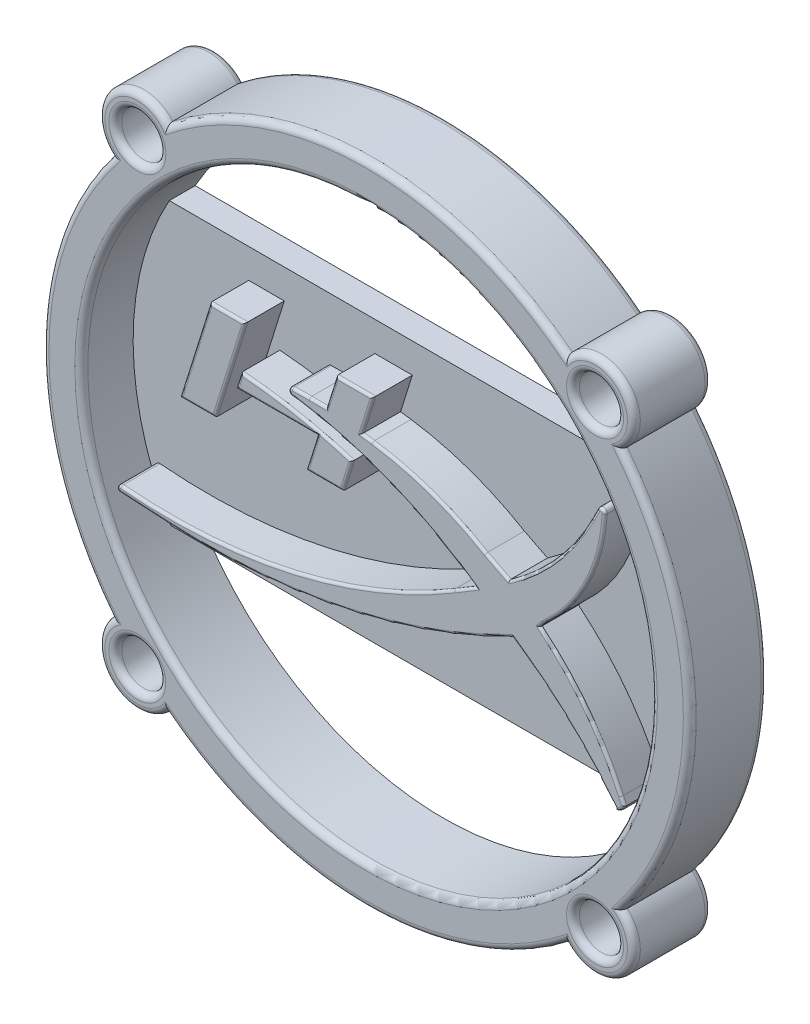
SolidWorks part; units mm, degrees
ref_plane "前视基准面" through (0, 0, 0) normal (0, 0, 1) x (1, 0, 0)
ref_plane "上视基准面" through (0, 0, 0) normal (0, 1, 0) x (1, 0, 0)
ref_plane "右视基准面" through (0, 0, 0) normal (1, 0, 0) x (0, 0, -1)
other "Configuration Table"
sketch "草图1" plane through (0, 0, 0) normal (0, 0, 1) x (1, 0, 0)
  line L0 (0, 0) -> (47.3992, 0) construction
  line L1 (0, 0) -> (0, 44.4048) construction
  line L2 (0, 0) -> (38.3112, 38.3112) construction
  line L3 (0, 0) -> (17.6777, -17.6777) construction
  circle A0 centre (0, 0) radius 25
  circle A1 centre (-17.6777, 17.6777) radius 3
  circle A2 centre (17.6777, 17.6777) radius 3
  circle A3 centre (17.6777, -17.6777) radius 3
  circle A4 centre (-17.6777, -17.6777) radius 3
  point P22 (0, 0)
  dimension "D1" = 50
  dimension "D4" = 6
  dimension "D2" = 45
  dimension "D3" = 45
  dimension "D6" = 17.6777
  dimension "D5" = 4
extrude "凸台-拉伸1" add sketch "草图1" along normal blind 6 contours A0 A1 | A4 A0 A3 A2 A1 | A0 A2 | A0 A2 | A0 A1 | A0 A4 | A0 A4 | A0 A3 | A0 A3 region at (0, 0, 0) region at (16.7548, 16.7548, 0) region at (18.5547, 18.5547, 0) region at (18.5547, -18.5547, 0) region at (16.7548, -16.7548, 0) region at (-16.7548, 16.7548, 0) region at (-18.5547, 18.5547, 0) region at (-18.5547, -18.5547, 0) region at (-16.7548, -16.7548, 0)
sketch "草图2" plane through (0, 0, 6) normal (0, 0, 1) x (1, 0, 0)
  arc A0 (-15.4329, 19.6679) -> (-19.6679, 15.4329) centre (-17.6777, 17.6777) ccw construction
  arc A1 (-15.4329, 19.6679) -> (-19.6679, 15.4329) centre (-17.6777, 17.6777) ccw
  circle A2 centre (17.6777, 17.6777) radius 1.7
  circle A3 centre (17.6777, -17.6777) radius 1.7
  circle A4 centre (-17.6777, -17.6777) radius 1.7
  circle A5 centre (-17.6777, 17.6777) radius 1.7
  arc A10 (-15.4329, 19.6679) -> (-19.6679, 15.4329) centre (-17.6777, 17.6777) ccw
  arc A11 (-19.6679, 15.4329) -> (-19.6679, -15.4329) centre (0, 0) ccw
  arc A12 (-19.6679, -15.4329) -> (-15.4329, -19.6679) centre (-17.6777, -17.6777) ccw
  arc A13 (-15.4329, -19.6679) -> (15.4329, -19.6679) centre (0, 0) ccw
  arc A14 (15.4329, -19.6679) -> (19.6679, -15.4329) centre (17.6777, -17.6777) ccw
  arc A15 (19.6679, -15.4329) -> (19.6679, 15.4329) centre (0, 0) ccw
  arc A16 (19.6679, 15.4329) -> (15.4329, 19.6679) centre (17.6777, 17.6777) ccw
  arc A17 (15.4329, 19.6679) -> (-15.4329, 19.6679) centre (0, 0) ccw
  arc A18 (-15.4329, 19.6679) -> (-19.6679, 15.4329) centre (-17.6777, 17.6777) ccw
  arc A19 (-19.6679, 15.4329) -> (-19.6679, -15.4329) centre (0, 0) ccw
  arc A20 (-19.6679, -15.4329) -> (-15.4329, -19.6679) centre (-17.6777, -17.6777) ccw
  arc A21 (-15.4329, -19.6679) -> (15.4329, -19.6679) centre (0, 0) ccw
  arc A22 (15.4329, -19.6679) -> (19.6679, -15.4329) centre (17.6777, -17.6777) ccw
  arc A23 (19.6679, -15.4329) -> (19.6679, 15.4329) centre (0, 0) ccw
  arc A24 (19.6679, 15.4329) -> (15.4329, 19.6679) centre (17.6777, 17.6777) ccw
  arc A25 (15.4329, 19.6679) -> (-15.4329, 19.6679) centre (0, 0) ccw
  point P29 (0, 0)
  dimension "D2" = 3.4
  dimension "D1" = 0
  dimension "D3" = 4
extrude "切除-拉伸1" cut sketch "草图2" against normal blind 10 contours A2 | A5 | A4 | A3 region at (17.6777, 17.6777, 6) region at (-17.6777, -17.6777, 6) region at (-17.6777, 17.6777, 6)
sketch "草图3" plane through (0, 0, 6) normal (0, 0, 1) x (1, 0, 0)
  circle A0 centre (0, 0) radius 22
  dimension "D1" = 44
extrude "切除-拉伸2" cut sketch "草图3" against normal blind 4
sketch "草图4" plane through (0, 0, 2) normal (0, 0, 1) x (1, 0, 0)
  line L12 (-661.2646, 397.6502) -> (-127.9313, 397.6502) construction
  line L13 (-13.0709, 8.458) -> (-15.4113, 0.9687)
  line L14 (-15.4113, 0.9687) -> (-12.6652, 0.9687)
  line L15 (-12.6652, 0.9687) -> (-10.3248, 8.458)
  line L16 (-10.3248, 8.458) -> (-13.0709, 8.458)
  line L17 (-11.0813, 3.7259) -> (-4.798, 3.7259)
  line L18 (-4.798, 3.7259) -> (-5.6596, 0.9687)
  line L19 (-5.6596, 0.9687) -> (-2.8202, 0.9687)
  line L20 (-2.8202, 0.9687) -> (-2.079, 3.3405)
  line L21 (-10.6668, 4.9923) -> (-11.0813, 3.7259)
  line L22 (-10.6668, 5.7986) -> (-8.2154, 5.5396)
  line L23 (7.4352, -0.3063) -> (5.7703, -1.3053)
  line L24 (-20.3872, -7.1825) -> (-20.1903, -7.7317)
  line L25 (-20.1903, -7.7317) -> (-16.1679, -7.9455)
  line L26 (10.3104, -2.2589) -> (11.388, -3.042)
  line L27 (18.9315, -9.2693) -> (18.6816, -8.7149)
  line L28 (17.4418, 10.7839) -> (16.3925, 8.7237)
  line L29 (10.0082, 1.4258) -> (8.2243, 2.3344)
  line L30 (-1.3401, 5.5396) -> (-0.4347, 8.4369)
  line L31 (-0.4347, 8.4369) -> (-3.3229, 8.4369)
  line L32 (-3.3229, 8.4369) -> (-4.0983, 5.9556)
  line L33 (-1.3401, 5.5396) -> (-0.5291, 5.4246)
  line L34 (-4.0983, 5.9556) -> (-5.3896, 5.9556)
  arc A0 (-2.079, 3.3405) -> (-10.6668, 4.9923) centre (-13.6595, -33.7171) ccw
  arc A1 (-8.2154, 5.5396) -> (7.4352, -0.3063) centre (-11.7323, -27.749) cw
  arc A2 (5.7703, -1.3053) -> (-20.3872, -7.1825) centre (-16.1938, 35.3015) cw
  arc A4 (-16.1679, -7.9455) -> (10.3104, -2.2589) centre (-13.4209, 43.7518) ccw
  arc A5 (11.388, -3.042) -> (18.3206, -9.8304) centre (-8.1571, -29.9365) cw
  arc A6 (18.3206, -9.8304) -> (18.9315, -9.2693) centre (18.1049, -8.9823) ccw
  arc A7 (18.6816, -8.7149) -> (12.3985, -0.5185) centre (-1.9231, -18.0034) ccw
  arc A8 (12.3985, -0.5185) -> (13.0039, 0.1288) centre (17.0125, -4.2268) cw
  arc A9 (13.0039, 0.1288) -> (17.4418, 10.7839) centre (3.6742, 10.2664) ccw
  arc A10 (16.3925, 8.7237) -> (10.0082, 1.4258) centre (-1.2323, 17.7004) cw
  arc A11 (-0.5291, 5.4246) -> (8.2243, 2.3344) centre (-3.8306, -17.8697) cw
  arc A12 (-5.3896, 5.9556) -> (-10.6668, 5.7986) centre (-5.3896, -82.7958) ccw
extrude "凸台-拉伸2" add sketch "草图4" along normal blind 3
fillet "圆角1" radius 0.3 4 edges at (-20.1903, -7.7317, 3.5) (-20.3872, -7.1825, 3.5) (17.4418, 10.7839, 3.5) (-10.6668, 5.7986, 3.5)
fillet "圆角2" radius 0.5 25 edges at (0, 25, 6) (19.799, 19.799, 6) (25, 0, 6) (19.799, -19.799, 6) (0, -25, 6) (-19.799, -19.799, 6) (-25, 0, 6) (-19.799, 19.799, 6) (19.3777, 17.6777, 6) (-15.9777, 17.6777, 6) (-15.9777, -17.6777, 6) (19.3777, -17.6777, 6) (22, 0, 6) (-25, 0, 0) (-19.799, -19.799, 0) (0, -25, 0) (19.799, -19.799, 0) (25, 0, 0) (19.799, 19.799, 0) (0, 25, 0) (-19.799, 19.799, 0) (19.3777, 17.6777, 0) (-15.9777, 17.6777, 0) (-15.9777, -17.6777, 0) (19.3777, -17.6777, 0)
fillet "圆角3" radius 0.2 36 edges at (-11.495, 4.7134, 5) (-14.0382, 0.9687, 5) (-14.2411, 4.7134, 5) (-11.6978, 8.458, 5) (-6.3262, 4.409, 5) (-2.4496, 2.1546, 5) (-4.2399, 0.9687, 5) (-5.2288, 2.3473, 5) (-7.9396, 3.7259, 5) (-10.874, 4.3591, 5) (-6.6062, -6.2984, 5) (6.6027, -0.8058, 5) (0.6776, 3.3395, 5) (-6.9876, 5.6663, 5) (-6.0412, 5.9532, 5) (-4.744, 5.9556, 5) (-3.7106, 7.1962, 5) (-1.8788, 8.4369, 5) (-0.8874, 6.9882, 5) (-0.9346, 5.4821, 5) (4.0015, 4.3155, 5) (9.1162, 1.8801, 5) (13.6545, 4.6775, 5) (16.6277, 9.1856, 5) (17.2085, 9.8011, 5) (16.1307, 4.3799, 5) (12.6891, -0.1835, 5) (16.0145, -4.253, 5) (18.8066, -8.9921, 5) (18.6968, -9.6269, 5) (15.1033, -6.1819, 5) (10.8492, -2.6504, 5) (-2.5503, -6.8643, 5) (-18.0795, -7.8439, 5) (-20.1363, -7.6958, 5) (-20.1693, -7.3249, 5)
sketch "草图5" plane through (0, 0, 2) normal (0, 0, 1) x (1, 0, 0)
  line L0 (-19.0823, -10.9482) -> (19.0823, -10.9482)
  line L1 (-19.2075, 10.7271) -> (19.2075, 10.7271)
  arc A0 (-19.0823, -10.9482) -> (19.0823, -10.9482) centre (0, 0) ccw
  circle A1 centre (0, 0) radius 22
  arc A2 (19.2075, 10.7271) -> (-19.2075, 10.7271) centre (0, 0) ccw
  dimension "D1" = 0
extrude "切除-拉伸3" cut sketch "草图5" against normal blind 10 contours A2 L1 | L0 A0
